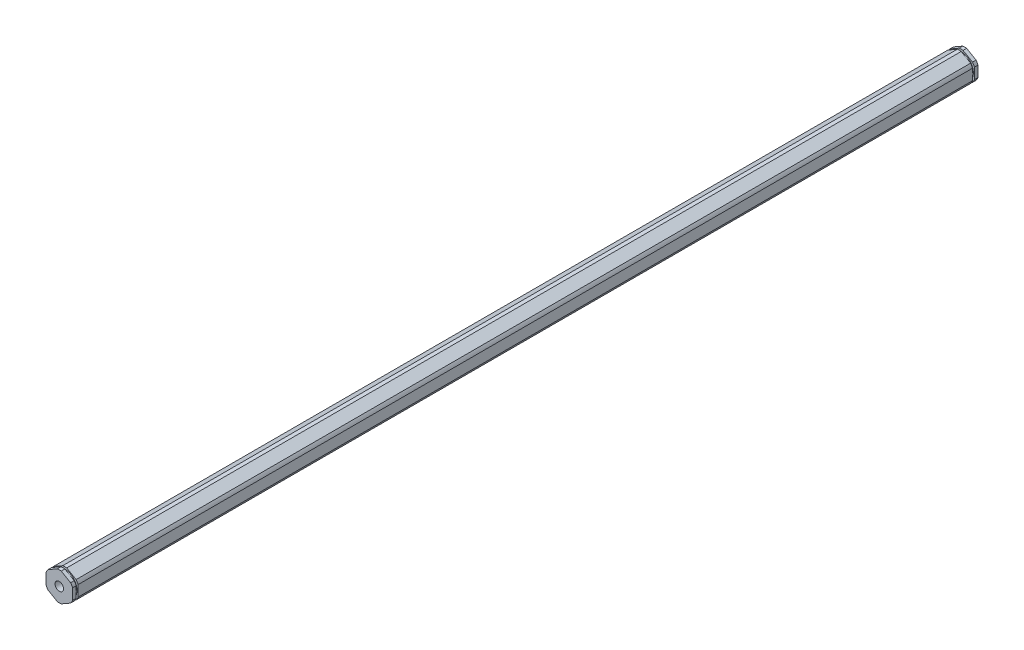
SolidWorks part; units mm, degrees
ref_plane "Front Plane" through (0, 0, 0) normal (0, 0, 1) x (1, 0, 0)
ref_plane "Top Plane" through (0, 0, 0) normal (0, 1, 0) x (1, 0, 0)
ref_plane "Right Plane" through (0, 0, 0) normal (1, 0, 0) x (0, 0, -1)
sketch "Sketch1" plane through (0, 0, 0) normal (0, 0, 1) x (1, 0, 0)
  line L1 (0, 7.3323) -> (-6.35, 3.6662)
  line L2 (-6.35, 3.6662) -> (-6.35, -3.6662)
  line L3 (-6.35, -3.6662) -> (0, -7.3323)
  line L4 (0, -7.3323) -> (6.35, -3.6662)
  line L5 (6.35, -3.6662) -> (6.35, 3.6662)
  line L6 (6.35, 3.6662) -> (0, 7.3323)
  circle A0 centre (0, 0) radius 6.35 construction
  circle A1 centre (0, 0) radius 6.858
  dimension "D1" = 12.7
  dimension "D2" = 13.716
extrude "Boss-Extrude1" add sketch "Sketch1" along normal mid plane 432.2343 contours L5 A1 L6 L1 L2 L3 L4 region at (0, 0, 0)
hole_wizard "#10-32 Tapped Hole1" positions "3DSketch1" profile "Sketch2" tap size "#10-32" standard "ANSI Inch"
sketch3d "3DSketch1"
  line L0 (0, 0, 216.1172) -> (0, 0, -216.1172) construction
  line L1 (0, 0, 216.1172) -> (0, 0, -216.1172) construction
  point P0 (0, 0, 216.1172)
  point P4 (0, 0, -216.1172)
sketch "Sketch2" plane through (0, 0, 216.1172) normal (1, 0, 0) x (0, -1, 0)
  line L0 (0, 0) -> (0, 17.5608)
  line L1 (0, 17.5608) -> (2.0193, 16.3474)
  line L2 (2.0193, 16.3474) -> (2.0193, 0)
  line L5 (2.0193, 0) -> (0, 0)
  line L10 (0, 17.5608) -> (-2.0193, 16.3474) construction
  line L11 (0, -6.35) -> (0, 107.95) construction
  dimension "Tap Drill Dia." = 4.0386
  dimension "Tap Drill Depth" = 16.3474
  dimension "Drill Angle" = 118
cosmetic thread "Hole Thread1" parameters "D1"=13.97, "D2"=4.826
cosmetic thread "Hole Thread2" parameters "D1"=13.97, "D2"=4.826
sketch "Sketch5" plane through (0, 0, 0) normal (1, 0, 0) x (0, 0, -1)
  line L0 (216.1172, 6.858) -> (-216.1172, 6.858) construction
  line L1 (-214.4027, 6.858) -> (-213.5137, 6.858)
  line L2 (-214.4027, 6.858) -> (-214.4027, 5.8547)
  line L3 (-214.4027, 5.8547) -> (-213.5137, 5.8547)
  line L4 (-213.5137, 6.858) -> (-213.5137, 5.8547)
  line L5 (-165.0472, 0) -> (-158.8423, 0) construction
  dimension "D1" = 5.8547
  dimension "D2" = 0.889
  dimension "D3" = 1.7145
revolve "Cut-Revolve1" cut sketch "Sketch5" angle 360 about L5
mirror "Mirror1" about plane through (0, 0, 0) normal (0, 0, 1) of "Cut-Revolve1"
